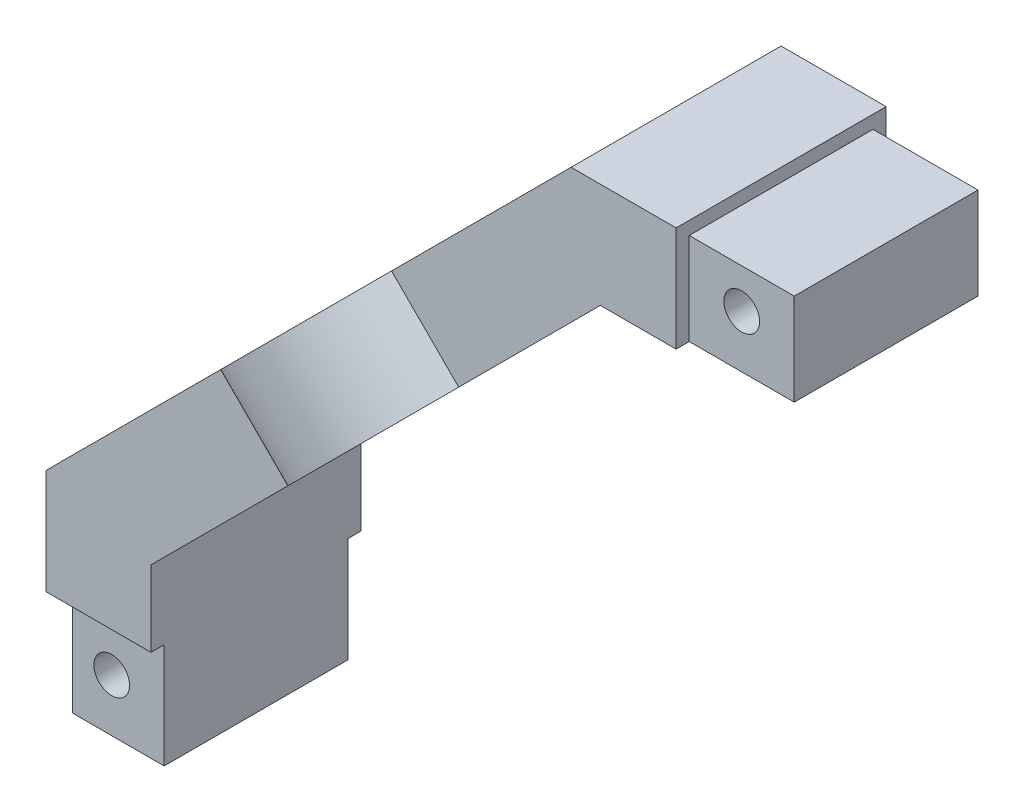
SolidWorks part; units mm, degrees
ref_plane "Front Plane" through (0, 0, 0) normal (0, 0, 1) x (1, 0, 0)
ref_plane "Top Plane" through (0, 0, 0) normal (0, 1, 0) x (1, 0, 0)
ref_plane "Right Plane" through (0, 0, 0) normal (1, 0, 0) x (0, 0, -1)
sketch "Sketch1" plane through (0, 0, 0) normal (0, 0, 1) x (1, 0, 0)
  line L0 (0, 0) -> (381, 0)
  line L1 (0, 0) -> (0, -381)
  line L2 (0, -12.7) -> (195.9668, -12.7)
  line L3 (15.1739, -73.5456) -> (73.5456, -15.1739)
  line L4 (15.1739, -73.5456) -> (33.1344, -91.5061)
  line L5 (33.1344, -91.5061) -> (91.5061, -33.1344)
  line L6 (73.5456, -15.1739) -> (91.5061, -33.1344)
  line L7 (15.1739, -73.5456) -> (91.5061, -33.1344) construction
  line L8 (33.1344, -91.5061) -> (73.5456, -15.1739) construction
  line L9 (12.7, 0) -> (12.7, -150.5133)
  line L10 (38.0736, -100.9354) -> (65.0143, -73.9946)
  line L15 (38.0736, -100.9354) -> (42.5637, -105.4255)
  line L16 (65.0143, -73.9946) -> (69.5045, -78.4847)
  line L21 (42.5637, -105.4255) -> (69.5045, -78.4847)
  line L22 (73.9946, -65.0143) -> (100.9354, -38.0736)
  line L27 (73.9946, -65.0143) -> (78.4847, -69.5045)
  line L28 (100.9354, -38.0736) -> (105.4255, -42.5637)
  line L29 (78.4847, -69.5045) -> (105.4255, -42.5637)
  line L30 (65.0143, -73.9946) -> (73.9946, -65.0143)
  line L31 (65.0143, -73.9946) -> (69.5045, -78.4847)
  line L32 (73.9946, -65.0143) -> (78.4847, -69.5045)
  line L33 (69.5045, -78.4847) -> (78.4847, -69.5045)
  line L34 (88.9, 0) -> (88.9, -25.4)
  line L35 (88.9, -25.4) -> (96.0842, -32.5842)
  line L36 (96.0842, -32.5842) -> (32.504, -96.1644)
  line L37 (0, -88.9) -> (25.4, -88.9)
  line L38 (25.4, -88.9) -> (32.504, -96.1644)
  line L39 (67.0392, -12.7) -> (12.7, -67.0392)
  line L40 (0, -63.5) -> (63.5, 0)
  line L41 (42.5637, -109.0176) -> (109.0176, -42.5637)
  line L42 (42.5637, -109.0176) -> (34.4815, -100.9354)
  line L43 (109.0176, -42.5637) -> (100.9354, -34.4815)
  line L44 (34.4815, -100.9354) -> (100.9354, -34.4815)
  line L45 (127, 0) -> (127, -50.8)
  line L46 (0, -127) -> (50.8, -127)
  line L47 (50.8, -127) -> (127, -50.8)
  line L48 (127, -1.5875) -> (88.9, -1.5875)
  line L49 (1.5875, -88.9) -> (1.5875, -127)
  point P3 (53.34, -53.34)
  point P33 (63.5, 0)
  point P34 (0, -63.5)
  dimension "D1" = 381
  dimension "D2" = 381
  dimension "D3" = 82.55
  dimension "D4" = 25.4
  dimension "D5" = 45
  dimension "D6" = 53.34
  dimension "D7" = 53.34
  dimension "D8" = 12.7
  dimension "D9" = 12.7
  dimension "D10" = 38.1
  dimension "D11" = 38.1
  dimension "D12" = 12.7
  dimension "D13" = 6.35
  dimension "D14" = 6.35
  dimension "D15" = 6.35
  dimension "D16" = 45
  dimension "D17" = 16.51
  dimension "D18" = 12.7
  dimension "D19" = 12.7
  dimension "D20" = 6.35
  dimension "D21" = 88.9
  dimension "D22" = 25.4
  dimension "D23" = 25.4
  dimension "D24" = 88.9
  dimension "D25" = 10.16
  dimension "D26" = 135
  dimension "D27" = 89.916
  dimension "D28" = 6.35
  dimension "D29" = 63.5
  dimension "D30" = 63.5
  dimension "D31" = 2.54
  dimension "D32" = 2.54
  dimension "D33" = 2.54
  dimension "D34" = 2.54
  dimension "D35" = 127
  dimension "D36" = 127
  dimension "D37" = 50.8
  dimension "D38" = 50.8
  dimension "D39" = 1.5875
  dimension "D40" = 1.5875
extrude "Boss-Extrude1" add sketch "Sketch1" along normal blind 25.4 contours L40 L9 L39 L2 | L40 L2 L34 L0 | L40 L1 L37 L9 region at (72.8133, -6.7733, 0) region at (6.7733, -72.8133, 0) region at (36.0475, -36.0475, 0)
sketch "Sketch2" plane through (0, 0, 25.4) normal (0, 0, 1) x (1, 0, 0)
  line L2 (88.9, 0) -> (76.2, 0)
  line L3 (88.9, 0) -> (88.9, -1.5875)
  line L4 (88.9, -1.5875) -> (76.2, -1.5875)
  line L5 (76.2, 0) -> (76.2, -1.5875)
  line L6 (0, -88.9) -> (1.5875, -88.9)
  line L7 (0, -88.9) -> (0, -76.2)
  line L8 (0, -76.2) -> (1.5875, -76.2)
  line L9 (1.5875, -88.9) -> (1.5875, -76.2)
  circle A0 centre (82.55, -6.3627) radius 2.159
  circle A1 centre (6.3627, -82.55) radius 2.159
  dimension "D1" = 4.318
  dimension "D2" = 4.318
  dimension "D3" = 82.55
  dimension "D4" = 82.55
  dimension "D5" = 4.7752
  dimension "D6" = 4.7752
  dimension "D7" = 1.5875
  dimension "D8" = 1.5875
  dimension "D9" = 12.7
  dimension "D10" = 12.7
extrude "Cut-Extrude1" cut sketch "Sketch2" against normal blind 25.4
sketch "Sketch3" plane through (0, -88.9, 0) normal (0, -1, 0) x (1, 0, 0)
  line L0 (0, 0) -> (0, 25.4) construction
  line L1 (12.7, 25.4) -> (0, 25.4)
  line L2 (12.7, 25.4) -> (12.7, 23.8125)
  line L3 (12.7, 23.8125) -> (0, 23.8125)
  line L4 (0, 25.4) -> (0, 23.8125)
  line L6 (12.7, 0) -> (0, 0)
  line L7 (12.7, 0) -> (12.7, 1.5748)
  line L8 (12.7, 1.5748) -> (0, 1.5748)
  line L9 (0, 0) -> (0, 1.5748)
  dimension "D1" = 1.5875
  dimension "D2" = 1.5748
extrude "Cut-Extrude2" cut sketch "Sketch3" against normal blind 12.7
sketch "Sketch4" plane through (88.9, 0, 0) normal (1, 0, 0) x (0, 0, -1)
  line L0 (0, 0) -> (-25.4, 0) construction
  line L1 (0, -12.7) -> (-1.5875, -12.7)
  line L2 (0, -12.7) -> (0, 0)
  line L3 (0, 0) -> (-1.5875, 0)
  line L4 (-1.5875, -12.7) -> (-1.5875, 0)
  line L6 (-25.4, -12.7) -> (-23.8125, -12.7)
  line L7 (-25.4, -12.7) -> (-25.4, 0)
  line L8 (-25.4, 0) -> (-23.8125, 0)
  line L9 (-23.8125, -12.7) -> (-23.8125, 0)
  dimension "D1" = 1.5875
  dimension "D2" = 1.5875
extrude "Cut-Extrude3" cut sketch "Sketch4" against normal blind 12.7
sketch3d "3DSketch1"
  line L0 (67.0392, -12.7, 0) -> (67.0392, -12.7, 25.4)
  line L1 (12.7, -67.0392, 0) -> (12.7, -67.0392, 25.4)
  line L2 (12.7, -67.0392, 0) -> (12.7, -76.2, 0) construction
  line L3 (12.7, -67.0392, 12.7) -> (67.0392, -12.7, 12.7)
  circle A0 centre (39.8696, -39.8696, 12.7) radius 11.1125
  circle A1 centre (39.8696, -39.8696, 12.7) radius 19.05
  point P2 (32.0119, -32.0119, 12.7)
  point P16 (26.3992, -26.3992, 12.7)
  dimension "D1" = 22.225
  dimension "D3" = 38.1
  dimension "D2" = 12.7
extrude "Boss-Extrude2" add sketch "3DSketch1" along direction (-0.7071, 0.7071, 0) on the side of the normal up to surface (11.4829 mm away) contours A1
extrude "Cut-Extrude4" cut sketch "3DSketch1<4>" along direction (0.7071, -0.7071, 0) on the side of the normal up to surface (11.4829 mm away) contours A0
sketch3d "3DSketch1<4>" same geometry as "3DSketch1"
